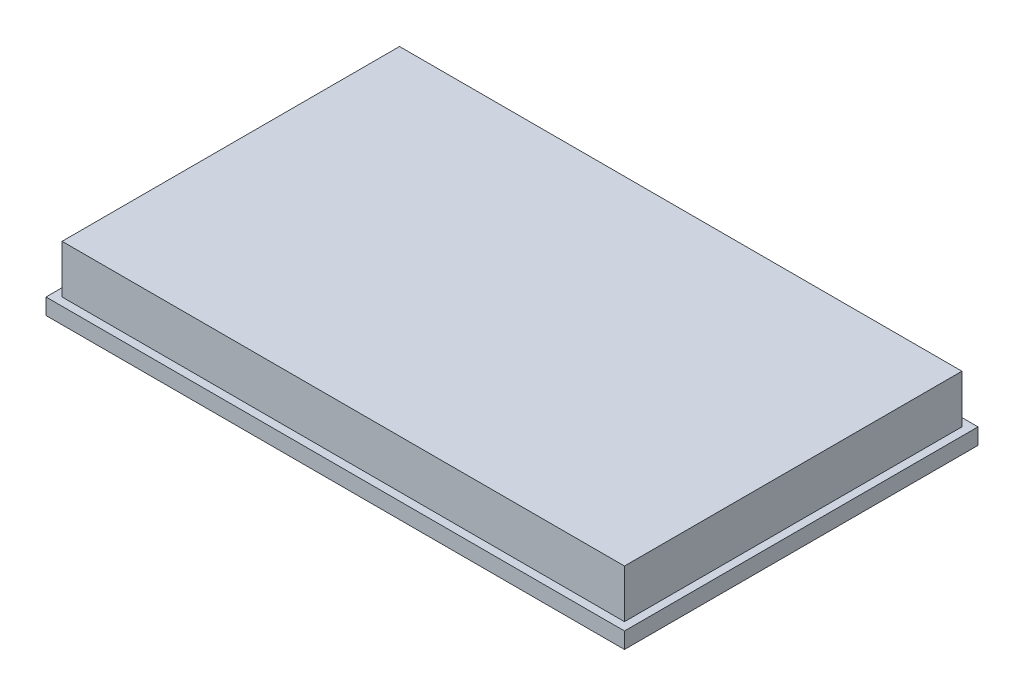
SolidWorks part; units mm, degrees
material "Gray Cast Iron"
ref_plane "Front Plane" through (0, 0, 0) normal (0, 0, 1) x (1, 0, 0)
ref_plane "Top Plane" through (0, 0, 0) normal (0, 1, 0) x (1, 0, 0)
ref_plane "Right Plane" through (0, 0, 0) normal (1, 0, 0) x (0, 0, -1)
sketch "Sketch1" plane through (0, 0, 0) normal (0, 1, 0) x (1, 0, 0)
  line L0 (-228.6, -139.7) -> (228.6, -139.7)
  line L1 (228.6, -139.7) -> (228.6, 139.7)
  line L2 (228.6, 139.7) -> (-228.6, 139.7)
  line L3 (-228.6, 139.7) -> (-228.6, -139.7)
extrude "Boss-Extrude1" add sketch "Sketch1" along normal blind 12.7
sketch "Sketch2" plane through (0, 0, 0) normal (0, 1, 0) x (1, 0, 0)
  line L0 (-222.25, -133.35) -> (222.25, -133.35)
  line L1 (222.25, -133.35) -> (222.25, 133.35)
  line L2 (222.25, 133.35) -> (-222.25, 133.35)
  line L3 (-222.25, 133.35) -> (-222.25, -133.35)
extrude "Boss-Extrude2" add sketch "Sketch2" along normal blind 38.1 from offset 12.7
